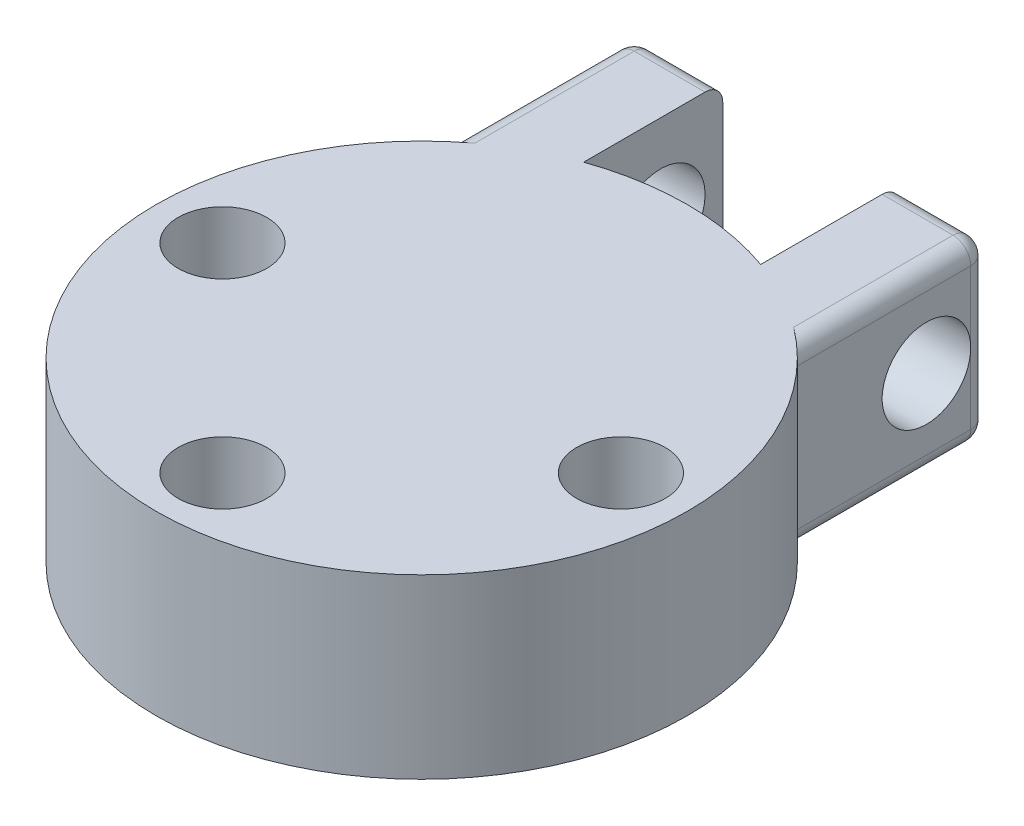
SolidWorks part; units mm, degrees
material "AISI 304"
ref_plane "Front Plane" through (0, 0, 0) normal (0, 0, 1) x (1, 0, 0)
ref_plane "Top Plane" through (0, 0, 0) normal (0, 1, 0) x (1, 0, 0)
ref_plane "Right Plane" through (0, 0, 0) normal (1, 0, 0) x (0, 0, -1)
sketch "Sketch1" plane through (0, 0, 0) normal (0, 1, 0) x (1, 0, 0)
  line L0 (-5, 14.1421) -> (-5, 22)
  line L1 (-5, 22) -> (-10, 22)
  line L2 (-10, 22) -> (-10, 11.1803)
  line L3 (0, 51.1072) -> (0, -46.9338) construction
  line L4 (5, 14.1421) -> (5, 22)
  line L5 (5, 22) -> (10, 22)
  line L6 (10, 22) -> (10, 11.1803)
  arc A0 (-10, 11.1803) -> (10, 11.1803) centre (0, 0) ccw
  arc A1 (5, 14.1421) -> (-5, 14.1421) centre (0, 0) ccw
  point P5 (0, 15)
  dimension "D1" = 30
  dimension "D2" = 5
  dimension "D3" = 5
  dimension "D4" = 7
extrude "Boss-Extrude1" add sketch "Sketch1" along normal blind 10
sketch "Sketch2" plane through (-10, 0, 0) normal (-1, 0, 0) x (0, 0, 1)
  line L1 (-22, 10) -> (-22, 0) construction
  line L2 (-22, 0) -> (-11.1803, 0) construction
  point P0 (-18.5, 5)
  dimension "D1" = 3.5
  dimension "D2" = 5
sketch "Sketch3" plane through (-10, 0, 0) normal (-1, 0, 0) x (0, 0, 1)
  point P0 (-18.5, 5)
hole_wizard "Ø5.0mm Dowel Hole1" positions "Sketch3" profile "Sketch4" hole size "Ø5.0" standard "ANSI Metric" end condition through all
sketch "Sketch4" plane through (-10, 5, -18.5) normal (0, 1, 0) x (0, 0, 1)
  line L0 (0, 0) -> (0, 25)
  line L1 (0, 25) -> (2.5, 25)
  line L2 (2.5, 25) -> (2.5, 0.025)
  line L3 (2.5, 0.025) -> (2.525, 0)
  line L5 (2.525, 0) -> (0, 0)
  line L6 (-2.5, 0.025) -> (-2.525, 0) construction
  line L11 (0, -6.35) -> (0, 107.95) construction
  dimension "Thru Hole Dia." = 5
  dimension "Thru Hole Depth" = 25
  dimension "Near C'Sink Dia." = 5.05
  dimension "Near C'Sink Angle" = 90
sketch "Sketch5" plane through (0, 0, -22) normal (0, 0, -1) x (-1, 0, 0)
  line L0 (-5, 0) -> (5, 0)
  line L1 (5, 0) -> (5, 7.5)
  line L2 (5, 10) -> (5, 0) construction
  line L3 (5, 7.5) -> (-5, 7.5)
  line L4 (-5, 10) -> (-5, 0) construction
  line L5 (-5, 7.5) -> (-5, 0)
  line L6 (5, 10) -> (-5, 10) construction
  dimension "D1" = 2.5
extrude "Cut-Extrude1" cut sketch "Sketch5" against normal blind 20
sketch "Sketch6" plane through (0, 0, 0) normal (0, -1, 0) x (1, 0, 0)
  circle A0 centre (0, 0) radius 7.5
  dimension "D1" = 15
extrude "Cut-Extrude2" cut sketch "Sketch6" against normal up to surface (7.5 mm away) up to face at (0, 7.5, -8.2855)
chamfer "Chamfer1" distance 2 angle 45 1 edges at (0, 7.5, -15)
fillet "Fillet1" radius 1 10 edges at (10, 0, -16.5902) (10, 5, -22) (7.5, 0, -22) (7.5, 10, -22) (10, 10, -16.5902) (-7.5, 0, -22) (-10, 0, -16.5902) (-10, 5, -22) (-10, 10, -16.5902) (-7.5, 10, -22)
sketch "Sketch7" plane through (0, 0, 0) normal (0, -1, 0) x (1, 0, 0)
  circle A0 centre (0, 0) radius 11.25 construction
  point P0 (-11.25, 0)
  point P1 (0, 11.25)
  point P2 (11.25, 0)
  dimension "D1" = 22.5
sketch "Sketch8" plane through (0, 0, 0) normal (0, -1, 0) x (-1, 0, 0)
  point P0 (-11.25, 0)
  point P3 (0, -11.25)
  point P6 (11.25, 0)
hole_wizard "Ø5.0mm Dowel Hole2" positions "Sketch8" profile "Sketch9" hole size "Ø5.0" standard "ANSI Metric"
sketch "Sketch9" plane through (11.25, 0, 0) normal (1, 0, 0) x (0, 0, -1)
  line L0 (0, 0) -> (0, 11.5022)
  line L1 (0, 11.5022) -> (2.5, 10)
  line L2 (2.5, 10) -> (2.5, 0)
  line L5 (2.5, 0) -> (0, 0)
  line L10 (0, 11.5022) -> (-2.5, 10) construction
  line L11 (0, -6.35) -> (0, 107.95) construction
  dimension "Hole Dia." = 5
  dimension "Hole Depth" = 10
  dimension "Drill Angle" = 118
